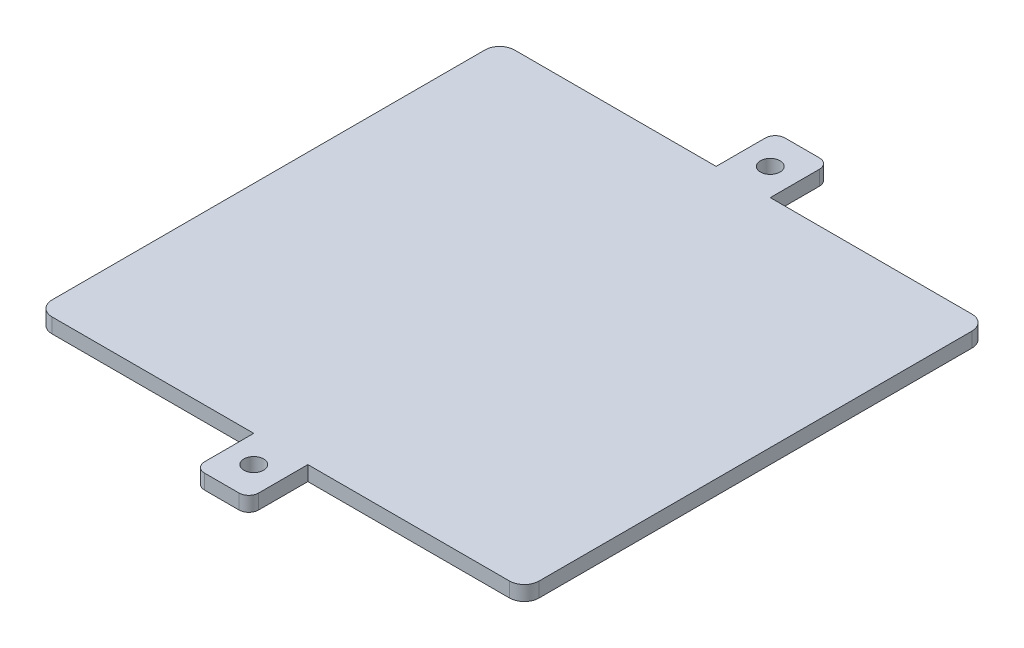
SolidWorks part; units mm, degrees
ref_plane "Plano frontal" through (0, 0, 0) normal (0, 0, 1) x (1, 0, 0)
ref_plane "Plano superior" through (0, 0, 0) normal (0, 1, 0) x (1, 0, 0)
ref_plane "Plano direito" through (0, 0, 0) normal (1, 0, 0) x (0, 0, -1)
sketch "Esboço1" plane through (0, 0, 0) normal (0, 1, 0) x (1, 0, 0)
  line L0 (0, -3) -> (93, -3)
  line L1 (0, 0) -> (93, 0) construction
  line L2 (0, 0) -> (0, 88) construction
  line L3 (0, 88) -> (93, 88) construction
  line L4 (93, 0) -> (93, 88) construction
  line L5 (-3, 0) -> (-3, 88)
  line L6 (0, 91) -> (93, 91)
  line L7 (96, 0) -> (96, 88)
  line L13 (46.5, 88) -> (46.5, 0) construction
  line L15 (0, 44) -> (93, 44) construction
  line L20 (0, 0) -> (93, 88) construction
  line L24 (96, 38.5) -> (96, 49.5)
  line L25 (43, 103) -> (50, 103)
  line L26 (41, -3) -> (52, -3)
  line L27 (41, -3) -> (41, -13)
  line L28 (43, -15) -> (50, -15)
  line L29 (52, -3) -> (52, -13)
  line L30 (52, 91) -> (52, 101)
  line L31 (41, 91) -> (52, 91)
  line L32 (41, 91) -> (41, 101)
  arc A3 (93, -3) -> (96, 0) centre (93, 0) ccw
  arc A4 (93, 91) -> (96, 88) centre (93, 88) cw
  arc A5 (-3, 88) -> (0, 91) centre (0, 88) cw
  arc A6 (0, -3) -> (-3, 0) centre (0, 0) cw
  arc A16 (50, -15) -> (52, -13) centre (50, -13) ccw
  arc A17 (41, -13) -> (43, -15) centre (43, -13) ccw
  circle A18 centre (46.5, -8.5) radius 2
  circle A19 centre (46.5, 96.5) radius 2
  arc A20 (50, 103) -> (52, 101) centre (50, 101) cw
  arc A21 (41, 101) -> (43, 103) centre (43, 101) cw
  point P15 (96, -3)
  point P24 (96, 91)
  dimension "D10" = 2
  dimension "D7" = 41
  dimension "D8" = 3
  dimension "D11" = 10
  dimension "D12" = 5.5
  dimension "D1" = 93
  dimension "D2" = 88
  dimension "D3" = 99
  dimension "D4" = 94
  dimension "D5" = 3
  dimension "D6" = 3
  dimension "D9" = 41
  dimension "D13" = 5.5
extrude "Ressalto-extrusão2" add sketch "Esboço1" along normal blind 3 contours L0 L7 L6 L5 L4 L1 L2 L3 region at (46.5, 0, -44)
extrude "Ressalto-extrusão3" add sketch "Esboço1<8>" along normal blind 3 contours L27 A17 L28 A16 L29 L0 A18 | A21 L32 L6 L30 A20 L25 A19 region at (46.5, 0, 3.1628) region at (41.1628, 0, -96)
sketch "Esboço1<8>" plane through (0, 0, 0) normal (0, 1, 0) x (1, 0, 0) same geometry as "Esboço1"
